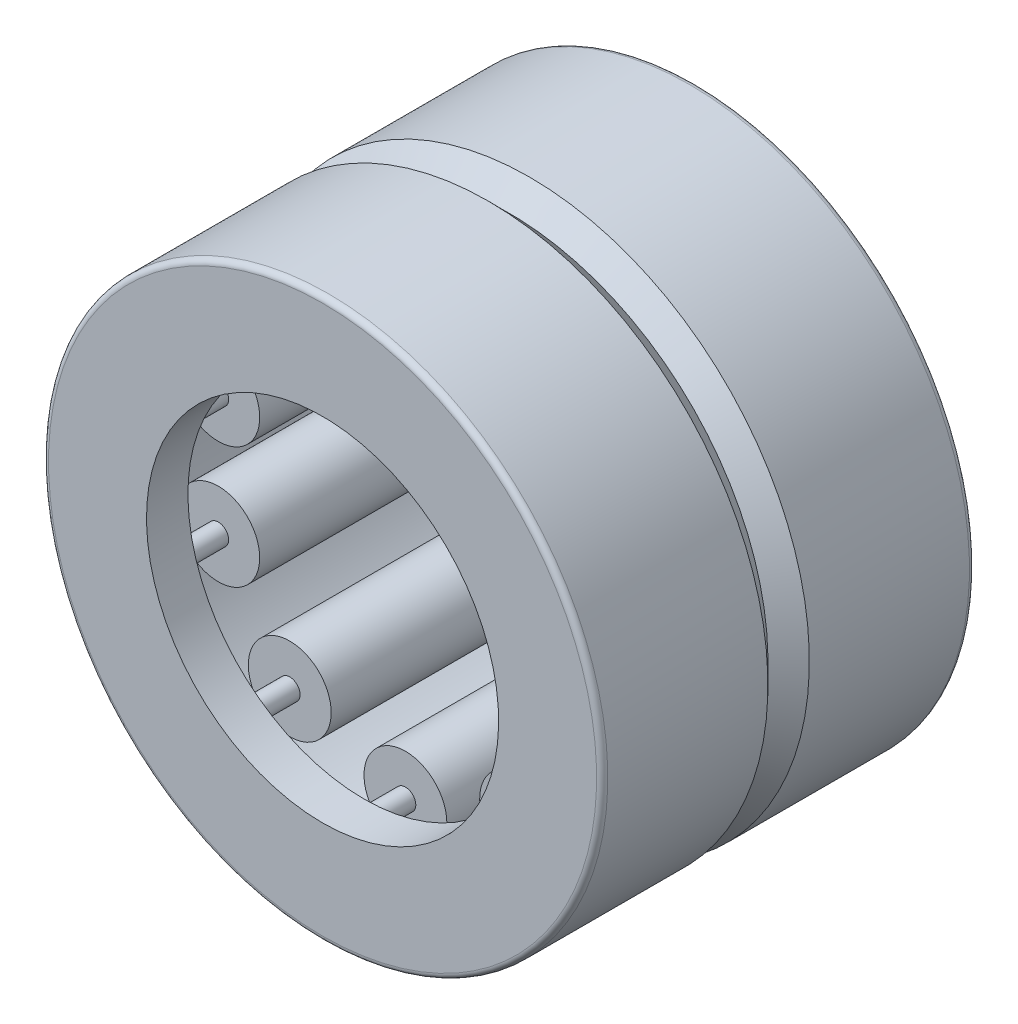
SolidWorks part; units mm, degrees
ref_plane "Front Plane" through (0, 0, 0) normal (0, 0, 1) x (1, 0, 0)
ref_plane "Top Plane" through (0, 0, 0) normal (0, 1, 0) x (1, 0, 0)
ref_plane "Right Plane" through (0, 0, 0) normal (1, 0, 0) x (0, 0, -1)
sketch "Sketch1" plane through (0, 0, 0) normal (1, 0, 0) x (0, 0, -1)
  line L0 (-9.525, 0) -> (9.525, 0) construction
  line L1 (0, 0) -> (0, 14.2875) construction
  line L2 (-9.525, 0) -> (-9.525, 14.2875) construction
  line L3 (-9.525, 14.2875) -> (9.525, 14.2875)
  line L4 (9.525, 14.2875) -> (9.525, 0) construction
  line L5 (9.525, 0) -> (7.4083, 0) construction
  line L6 (7.4083, 0) -> (7.4083, 12.1708) construction
  line L7 (7.4083, 12.1708) -> (-7.4083, 12.1708)
  line L8 (-7.4083, 12.1708) -> (-7.4083, 0) construction
  line L9 (-7.4083, 0) -> (-9.525, 0) construction
  line L10 (-9.525, 14.2875) -> (-9.525, 8.9958)
  line L11 (-9.525, 8.9958) -> (-7.4083, 8.9958)
  line L12 (-7.4083, 8.9958) -> (-7.4083, 12.1708)
  line L13 (7.4083, 14.2875) -> (7.4083, 12.1708) construction
  line L14 (7.4083, 12.1708) -> (7.4083, 8.9958)
  line L15 (7.4083, 8.9958) -> (9.525, 8.9958)
  line L16 (9.525, 8.9958) -> (9.525, 14.2875)
  line L17 (7.4083, 12.1708) -> (7.4083, 10.0542) construction
  line L18 (7.4083, 10.0542) -> (7.4083, 7.9375) construction
  line L19 (7.4083, -12.1708) -> (7.4083, -10.0542) construction
  line L20 (7.4083, -14.2875) -> (7.4083, -12.1708) construction
  line L21 (9.525, -8.9958) -> (9.525, -14.2875) construction
  line L22 (7.4083, -8.9958) -> (9.525, -8.9958) construction
  line L23 (7.4083, -12.1708) -> (7.4083, -8.9958) construction
  line L24 (-7.4083, -8.9958) -> (-7.4083, -12.1708) construction
  line L25 (-9.525, -8.9958) -> (-7.4083, -8.9958) construction
  line L26 (-9.525, -14.2875) -> (-9.525, -8.9958) construction
  line L27 (7.4083, -12.1708) -> (-7.4083, -12.1708) construction
  line L28 (-9.525, -14.2875) -> (9.525, -14.2875) construction
  point P5 (0, 7.9375)
  dimension "Width" = 19.05
  dimension "OD" = 28.575
  dimension "Shaft Dia" = 15.875
revolve "Revolve1" add sketch "Sketch1" angle 360 about L0
sketch "Sketch2" plane through (0, 0, 0) normal (1, 0, 0) x (0, 0, -1)
  line L0 (7.4083, 12.1708) -> (-7.4083, 12.1708) construction
  line L1 (-5.2917, 10.0542) -> (5.2917, 10.0542) construction
  line L2 (-5.2917, 10.0542) -> (-5.2917, 12.1708) construction
  line L3 (-5.2917, 12.1708) -> (5.2917, 12.1708)
  line L4 (5.2917, 10.0542) -> (5.2917, 12.1708) construction
  line L5 (7.4083, 8.9958) -> (9.525, 8.9958) construction
  line L6 (-7.4083, 10.0542) -> (-5.2917, 10.0542) construction
  line L7 (5.2917, 10.0542) -> (7.4083, 10.0542) construction
  line L8 (-9.525, 8.9958) -> (-7.4083, 8.9958) construction
  line L9 (-5.2917, 10.5833) -> (-5.2917, 9.525) construction
  line L10 (-7.4083, 10.0542) -> (-7.4083, 8.9958) construction
  line L11 (-5.2917, 12.1708) -> (-5.2917, 10.5833)
  line L12 (5.2917, 12.1708) -> (5.2917, 10.5833)
  line L13 (5.2917, 10.5833) -> (-5.2917, 10.5833)
  line L14 (0, 12.1708) -> (0, 7.9375) construction
  line L15 (-7.4083, 8.9958) -> (-7.4083, 12.1708) construction
  line L16 (-5.2917, 9.525) -> (-7.4083, 9.525) construction
  line L17 (0, 0) -> (9.525, 0) construction
  line L18 (9.525, -14.2875) -> (9.525, 14.2875) construction
  line L19 (-5.2917, -9.525) -> (-7.4083, -9.525) construction
  line L20 (0, -12.1708) -> (0, -7.9375) construction
  line L21 (-7.4083, -10.0542) -> (-7.4083, -8.9958) construction
  line L22 (-5.2917, -10.5833) -> (-5.2917, -9.525) construction
  line L23 (5.2917, -10.0542) -> (7.4083, -10.0542) construction
  line L24 (-7.4083, -10.0542) -> (-5.2917, -10.0542) construction
  line L25 (5.2917, -10.0542) -> (5.2917, -12.1708) construction
  line L26 (-5.2917, -10.0542) -> (-5.2917, -12.1708) construction
  line L27 (-5.2917, -10.0542) -> (5.2917, -10.0542) construction
  line L28 (5.2917, -10.5833) -> (-5.2917, -10.5833) construction
  line L29 (5.2917, -12.1708) -> (5.2917, -10.5833) construction
  line L30 (-5.2917, -12.1708) -> (-5.2917, -10.5833) construction
  line L31 (-5.2917, -12.1708) -> (5.2917, -12.1708) construction
  line L32 (-7.4083, 12.1708) -> (-7.4083, 0) construction
  point P16 (0, 10.0542)
revolve "Revolve2" add sketch "Sketch2" angle 360 about L1
sketch "Sketch3" plane through (0, 0, 0) normal (1, 0, 0) x (0, 0, -1)
  line L0 (7.4083, 12.1708) -> (7.4083, 8.9958) construction
  line L1 (-7.4083, 10.0542) -> (7.4083, 10.0542)
  line L2 (-7.4083, 10.0542) -> (-7.4083, 10.5833)
  line L3 (-7.4083, 10.5833) -> (7.4083, 10.5833)
  line L4 (7.4083, 10.0542) -> (7.4083, 10.5833)
  line L5 (0, 0) -> (9.525, 0) construction
  line L6 (9.525, -14.2875) -> (9.525, 14.2875) construction
  line L7 (7.4083, -10.0542) -> (7.4083, -10.5833) construction
  line L8 (-7.4083, -10.5833) -> (7.4083, -10.5833) construction
  line L9 (-7.4083, -10.0542) -> (-7.4083, -10.5833) construction
  line L10 (-7.4083, -10.0542) -> (7.4083, -10.0542) construction
revolve "Revolve3" add sketch "Sketch3" angle 360 about L1
ref_axis "Axis1" through (0, 0, -9.525) along (0, 0, 1)
pattern_circular "CirPattern1" count 10 over 360 about axis through (0, 0, -9.525) along (0, 0, 1) of bodies 167 166
fillet "Fillet1" radius 0.2858 2 edges at (0, -14.2875, -9.525) (0, -14.2875, 9.525)
sketch "Sketch4" plane through (0, 0, 0) normal (1, 0, 0) x (0, 0, -1)
  line L0 (-1.0583, 14.2875) -> (0, 13.2292)
  line L1 (-9.525, 14.2875) -> (9.525, 14.2875) construction
  line L2 (0, 0) -> (0, 14.2875) construction
  line L3 (0, 13.2292) -> (1.0583, 14.2875)
  line L4 (1.0583, 14.2875) -> (-1.0583, 14.2875)
  line L5 (0, 14.2875) -> (0, 12.1708) construction
revolve "Cut-Revolve1" cut sketch "Sketch4" angle 360 about L0
equation "\"Angle@CirPattern1\" = 360/\"Rollers@CirPattern1\""
equation "\"Rollers@CirPattern1\" = \"OD@Sketch1\"*9"
equation "\"D1@Fillet1\" = \"OD@Sketch1\"*.01"
